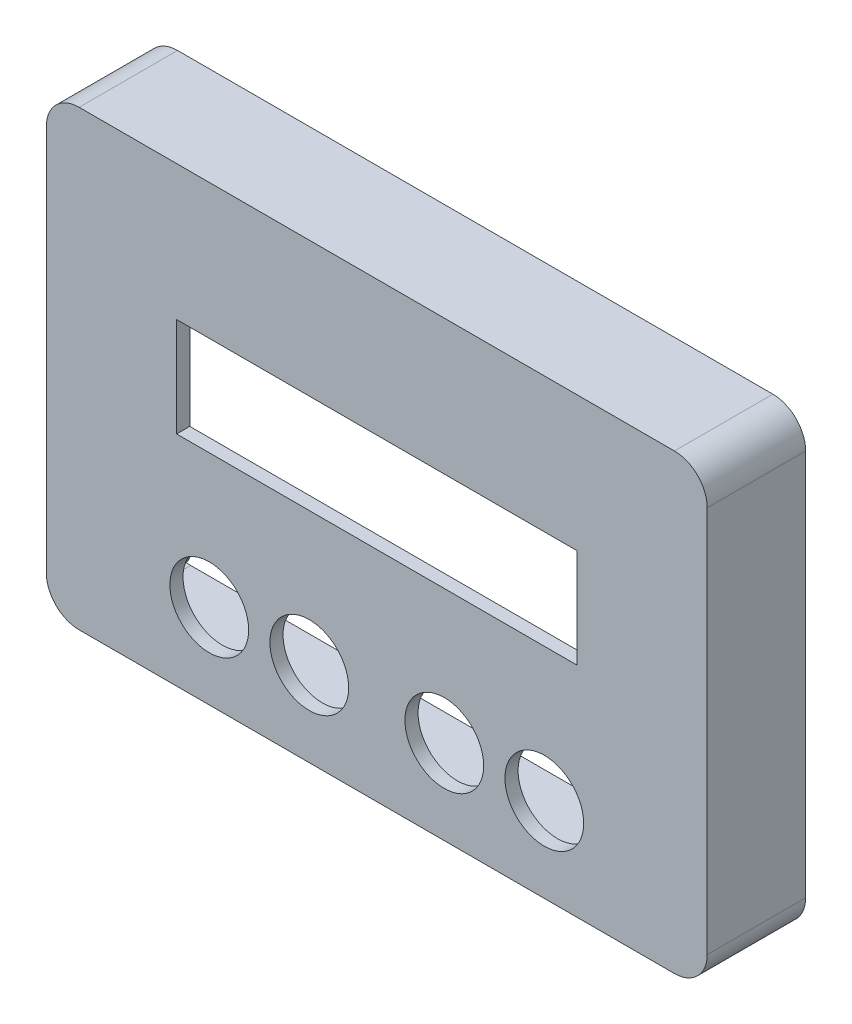
SolidWorks part; units mm, degrees
ref_plane "Front Plane" through (0, 0, 0) normal (0, 0, 1) x (1, 0, 0)
ref_plane "Top Plane" through (0, 0, 0) normal (0, 1, 0) x (1, 0, 0)
ref_plane "Right Plane" through (0, 0, 0) normal (1, 0, 0) x (0, 0, -1)
sketch "PCB" plane through (0, 0, 0) normal (0, 0, 1) x (1, 0, 0)
  line L1 (0, 0) -> (92.71, 0) construction
  line L2 (0, 0) -> (0, 60.96) construction
  line L3 (0, 60.96) -> (92.71, 60.96) construction
  line L4 (92.71, 0) -> (92.71, 60.96) construction
  line L5 (5.08, 55.88) -> (87.63, 55.88) construction
  line L6 (5.08, 55.88) -> (5.08, 5.08) construction
  line L7 (5.08, 5.08) -> (87.63, 5.08) construction
  line L8 (87.63, 55.88) -> (87.63, 5.08) construction
  circle A0 centre (5.08, 55.88) radius 1.5 construction
  circle A1 centre (87.63, 55.88) radius 1.5 construction
  circle A2 centre (5.08, 5.08) radius 1.5 construction
  circle A3 centre (87.63, 5.08) radius 1.5 construction
  dimension "D3" = 3
  dimension "D1" = 92.71
  dimension "D2" = 82.55
  dimension "D4" = 50.8
  dimension "D5" = 5.08
  dimension "D6" = 5.08
  dimension "D7" = 60.96
sketch "Sketch7" plane through (0, 0, 0) normal (0, 0, 1) x (1, 0, 0)
  line L0 (0, 60.96) -> (92.71, 60.96) construction
  line L1 (-4, -4) -> (96.71, -4)
  line L2 (-4, -4) -> (-4, 64.96)
  line L3 (-4, 64.96) -> (96.71, 64.96)
  line L4 (96.71, -4) -> (96.71, 64.96)
  line L5 (0, 0) -> (0, 60.96) construction
  dimension "D1" = 100.71
  dimension "D2" = 68.96
  dimension "D3" = 4
  dimension "D4" = 4
extrude "Boss-Extrude2" add sketch "Sketch7" along normal blind 15
sketch "Sketch8" plane through (0, 0, 15) normal (0, 0, 1) x (1, 0, 0)
  line L0 (0, 8.889) -> (92.71, 8.889) construction
  line L1 (15.855, 44.38) -> (76.855, 44.38)
  line L2 (15.855, 44.38) -> (15.855, 29.28)
  line L3 (15.855, 29.28) -> (76.855, 29.28)
  line L4 (76.855, 44.38) -> (76.855, 29.28)
  line L5 (0, 0) -> (0, 60.96) construction
  line L6 (92.71, 0) -> (92.71, 60.96) construction
  line L7 (0, 0) -> (92.71, 0) construction
  line L8 (0, 60.96) -> (92.71, 60.96) construction
  circle A0 centre (20.828, 8.889) radius 6
  circle A1 centre (36.068, 8.889) radius 6
  circle A2 centre (56.642, 8.889) radius 6
  circle A3 centre (71.882, 8.889) radius 6
  point P20 (0, 0)
  dimension "D3" = 12
  dimension "D1" = 61
  dimension "D2" = 15.1
  dimension "D4" = 8.889
  dimension "D5" = 20.828
  dimension "D6" = 20.828
  dimension "D7" = 15.24
  dimension "D8" = 15.24
  dimension "D9" = 20.574
  dimension "D10" = 15.855
  dimension "D11" = 16.58
extrude "Cut-Extrude1" cut sketch "Sketch8" against normal blind 5
sketch "Sketch9" plane through (0, 0, 0) normal (0, 0, -1) x (-1, 0, 0)
  line L0 (-96.71, 64.96) -> (4, 64.96) construction
  line L1 (-94.71, 62.96) -> (2, 62.96)
  line L2 (-94.71, 62.96) -> (-94.71, -2)
  line L3 (-94.71, -2) -> (2, -2)
  line L4 (2, 62.96) -> (2, -2)
  line L5 (-96.71, -4) -> (-96.71, 64.96) construction
  dimension "D1" = 96.71
  dimension "D2" = 64.96
  dimension "D3" = 2
  dimension "D4" = 2
extrude "Cut-Extrude2" cut sketch "Sketch9" against normal blind 13
sketch "Sketch10" plane through (0, 0, 13) normal (0, 0, -1) x (-1, 0, 0)
  circle A0 centre (-5.08, 55.88) radius 3
  circle A1 centre (-87.63, 55.88) radius 3
  circle A2 centre (-5.08, 5.08) radius 3
  circle A3 centre (-87.63, 5.08) radius 3
  circle A4 centre (-87.63, 55.88) radius 1.5
  circle A5 centre (-5.08, 55.88) radius 1.5
  circle A6 centre (-87.63, 5.08) radius 1.5
  circle A7 centre (-5.08, 5.08) radius 1.5
  dimension "D1" = 6
  dimension "D2" = 3
extrude "Boss-Extrude4" add sketch "Sketch10" along normal blind 8
thread "Thread1" pitch 0.5 start angle 0, offset 0, length 8, pitch 0.5, diameter 3
ref_plane "Plane2" through (89.13, 55.88, 5) normal (0, -1, 0) x (1, 0, 0)
sketch "Thread Profile2" plane through (89.13, 55.88, 5) normal (0, -1, 0) x (1, 0, 0)
  line L0 (0, 0) -> (0, 0.5) construction
  line L11 (0, 0) -> (0, 0.4375)
  line L12 (0, 0.4375) -> (-0.2706, 0.2812)
  line L13 (-0.2706, 0.2812) -> (-0.2706, 0.1562)
  line L15 (-0.2706, 0.1562) -> (0, 0)
  line L17 (-0.2706, 0.2187) -> (0, 0.2187) construction
  point P2 (0, 0)
  dimension "Pitch" = 0.5
  dimension "Profile_Angle" = 60
  dimension "Profile_Land" = 0.125
  dimension "Profile_Height" = 0.2706
thread "Thread2" pitch 0.5 profile "Thread Profile3" start angle 0, offset 0, length 8, pitch 0.5, diameter 3
ref_plane "Plane3" through (6.58, 55.88, 5) normal (0, -1, 0) x (1, 0, 0)
sketch "Thread Profile3" plane through (6.58, 55.88, 5) normal (0, -1, 0) x (1, 0, 0)
  line L0 (0, 0) -> (0, 0.5) construction
  line L11 (0, 0) -> (0, 0.4375)
  line L12 (0, 0.4375) -> (-0.2706, 0.2812)
  line L13 (-0.2706, 0.2812) -> (-0.2706, 0.1562)
  line L15 (-0.2706, 0.1562) -> (0, 0)
  line L17 (-0.2706, 0.2187) -> (0, 0.2187) construction
  point P2 (0, 0)
  dimension "Pitch" = 0.5
  dimension "Profile_Angle" = 60
  dimension "Profile_Land" = 0.125
  dimension "Profile_Height" = 0.2706
thread "Thread3" pitch 0.5 profile "Thread Profile4" start angle 0, offset 0, length 8, pitch 0.5, diameter 3
ref_plane "Plane4" through (89.13, 5.08, 5) normal (0, -1, 0) x (1, 0, 0)
sketch "Thread Profile4" plane through (89.13, 5.08, 5) normal (0, -1, 0) x (1, 0, 0)
  line L0 (0, 0) -> (0, 0.5) construction
  line L11 (0, 0) -> (0, 0.4375)
  line L12 (0, 0.4375) -> (-0.2706, 0.2812)
  line L13 (-0.2706, 0.2812) -> (-0.2706, 0.1562)
  line L15 (-0.2706, 0.1562) -> (0, 0)
  line L17 (-0.2706, 0.2187) -> (0, 0.2187) construction
  point P2 (0, 0)
  dimension "Pitch" = 0.5
  dimension "Profile_Angle" = 60
  dimension "Profile_Land" = 0.125
  dimension "Profile_Height" = 0.2706
thread "Thread4" pitch 0.5 profile "Thread Profile5" start angle 0, offset 0, length 8, pitch 0.5, diameter 3
ref_plane "Plane5" through (6.58, 5.08, 5) normal (0, -1, 0) x (1, 0, 0)
sketch "Thread Profile5" plane through (6.58, 5.08, 5) normal (0, -1, 0) x (1, 0, 0)
  line L0 (0, 0) -> (0, 0.5) construction
  line L11 (0, 0) -> (0, 0.4375)
  line L12 (0, 0.4375) -> (-0.2706, 0.2812)
  line L13 (-0.2706, 0.2812) -> (-0.2706, 0.1562)
  line L15 (-0.2706, 0.1562) -> (0, 0)
  line L17 (-0.2706, 0.2187) -> (0, 0.2187) construction
  point P2 (0, 0)
  dimension "Pitch" = 0.5
  dimension "Profile_Angle" = 60
  dimension "Profile_Land" = 0.125
  dimension "Profile_Height" = 0.2706
fillet "Fillet1" radius 5 8 edges at (-2, -2, 6.5) (-2, 62.96, 6.5) (94.71, -2, 6.5) (94.71, 62.96, 6.5) (-4, 64.96, 7.5) (-4, -4, 7.5) (96.71, -4, 7.5) (96.71, 64.96, 7.5)
